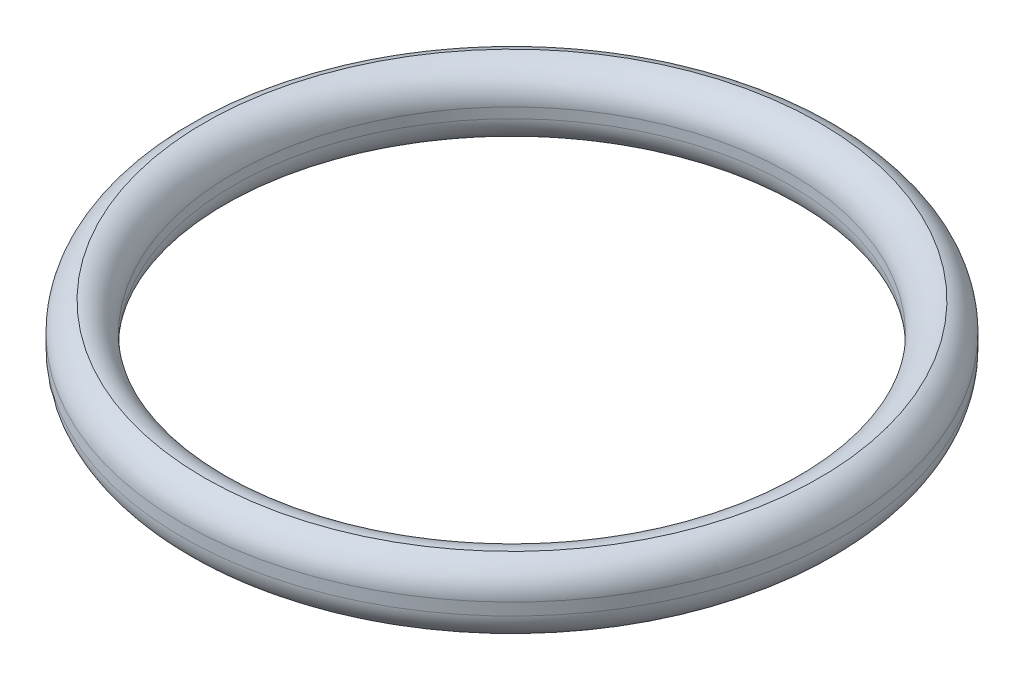
SolidWorks part; units mm, degrees
ref_plane "Front Plane" through (0, 0, 0) normal (0, 0, 1) x (1, 0, 0)
ref_plane "Top Plane" through (0, 0, 0) normal (0, 1, 0) x (1, 0, 0)
ref_plane "Right Plane" through (0, 0, 0) normal (1, 0, 0) x (0, 0, -1)
sketch "Sketch3" plane through (0, 0, 0) normal (0, 1, 0) x (1, 0, 0)
  circle A0 centre (0, 0) radius 22.5
  circle A1 centre (0, 0) radius 19
  dimension "D1" = 38
  dimension "D2" = 3.5
extrude "Boss-Extrude1" add sketch "Sketch3" along normal blind 4.7
fillet "Fillet1" radius 2 2 edges at (0, 0, 19) (0, 4.7, 19)
fillet "Fillet2" radius 2 2 edges at (0, 0, 22.5) (0, 4.7, 22.5)
